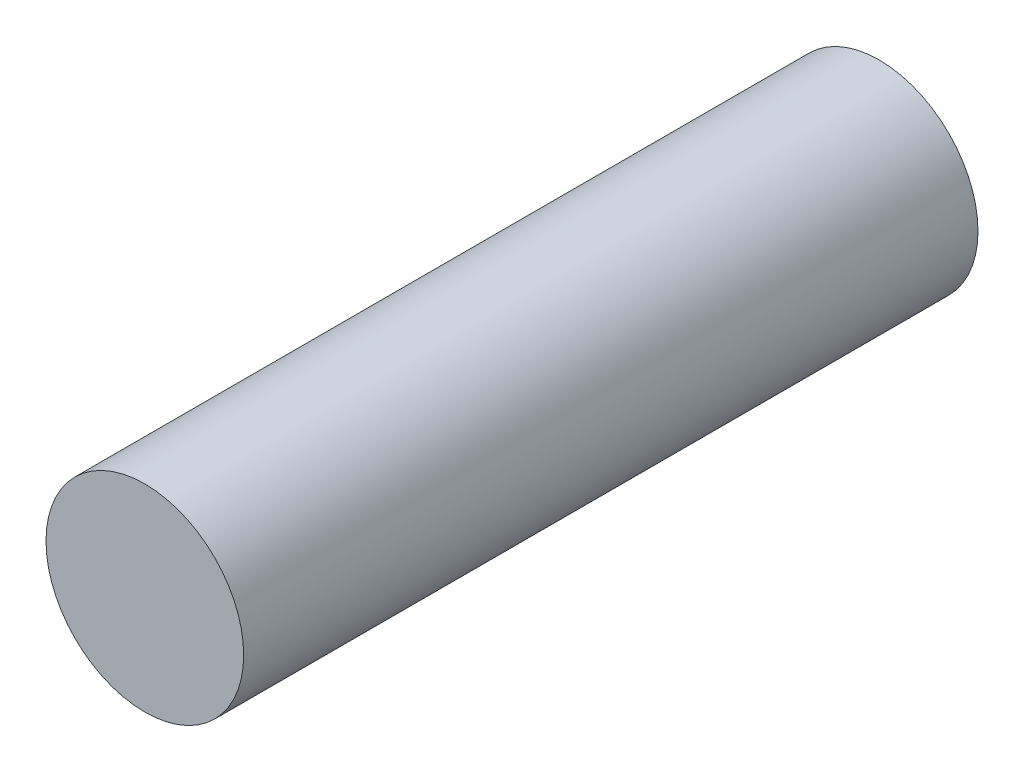
SolidWorks part; units mm, degrees
ref_plane "Front Plane" through (0, 0, 0) normal (0, 0, 1) x (1, 0, 0)
ref_plane "Top Plane" through (0, 0, 0) normal (0, 1, 0) x (1, 0, 0)
ref_plane "Right Plane" through (0, 0, 0) normal (1, 0, 0) x (0, 0, -1)
sketch "Sketch1" plane through (0, 0, 0) normal (0, 0, 1) x (1, 0, 0)
  circle A0 centre (0, 0) radius 2.49
  dimension "D1" = 4.98
extrude "Boss-Extrude1" add sketch "Sketch1" along normal mid plane 18.5
sketch "Sketch2" plane through (0, 0, 0) normal (0, 0, 1) x (1, 0, 0)
  circle A0 centre (0, 0) radius 2.5 construction
  dimension "D1" = 5
